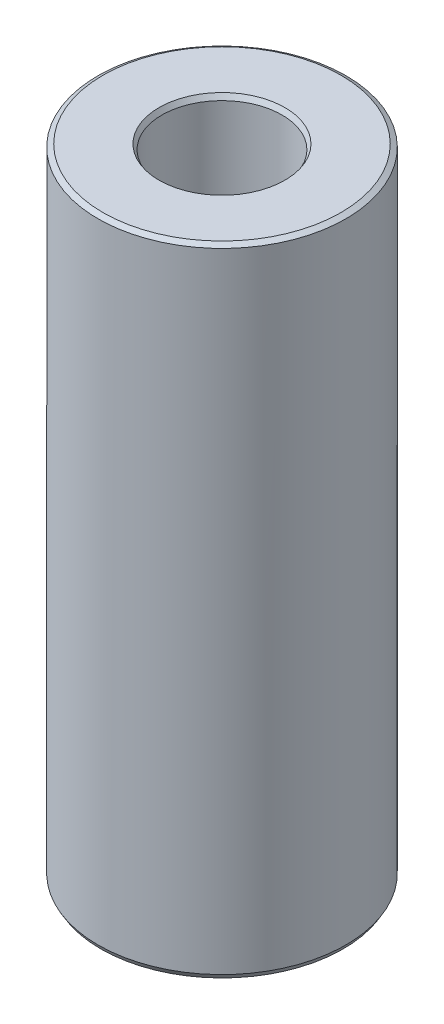
SolidWorks part; units mm, degrees
ref_plane "Front Plane" through (0, 0, 0) normal (0, 0, 1) x (1, 0, 0)
ref_plane "Top Plane" through (0, 0, 0) normal (0, 1, 0) x (1, 0, 0)
ref_plane "Right Plane" through (0, 0, 0) normal (1, 0, 0) x (0, 0, -1)
sketch "Sketch1" plane through (0, 0, 0) normal (0, 1, 0) x (1, 0, 0)
  circle A0 centre (0, 0) radius 45
  dimension "SLEEVE_OD" = 90
extrude "Boss-Extrude1" add sketch "Sketch1" along normal blind 231.1231
sketch "Sketch2" plane through (0, 0, 0) normal (0, 1, 0) x (1, 0, 0)
  circle A0 centre (0, 0) radius 21.8089
  dimension "BORE_D" = 43.6177
extrude "Cut-Extrude1" cut sketch "Sketch2" along normal through all
chamfer "Chamfer1" distance 1.0431 angle 60 4 edges at (0, 231.1231, 21.8089) (0, 0, 21.8089) (0, 0, 45) (0, 231.1231, 45) first distance on face at (0, 231.1231, 21.8089) first distance on face at (0, 0, 21.8089) first distance on face at (0, 231.1231, 45)
